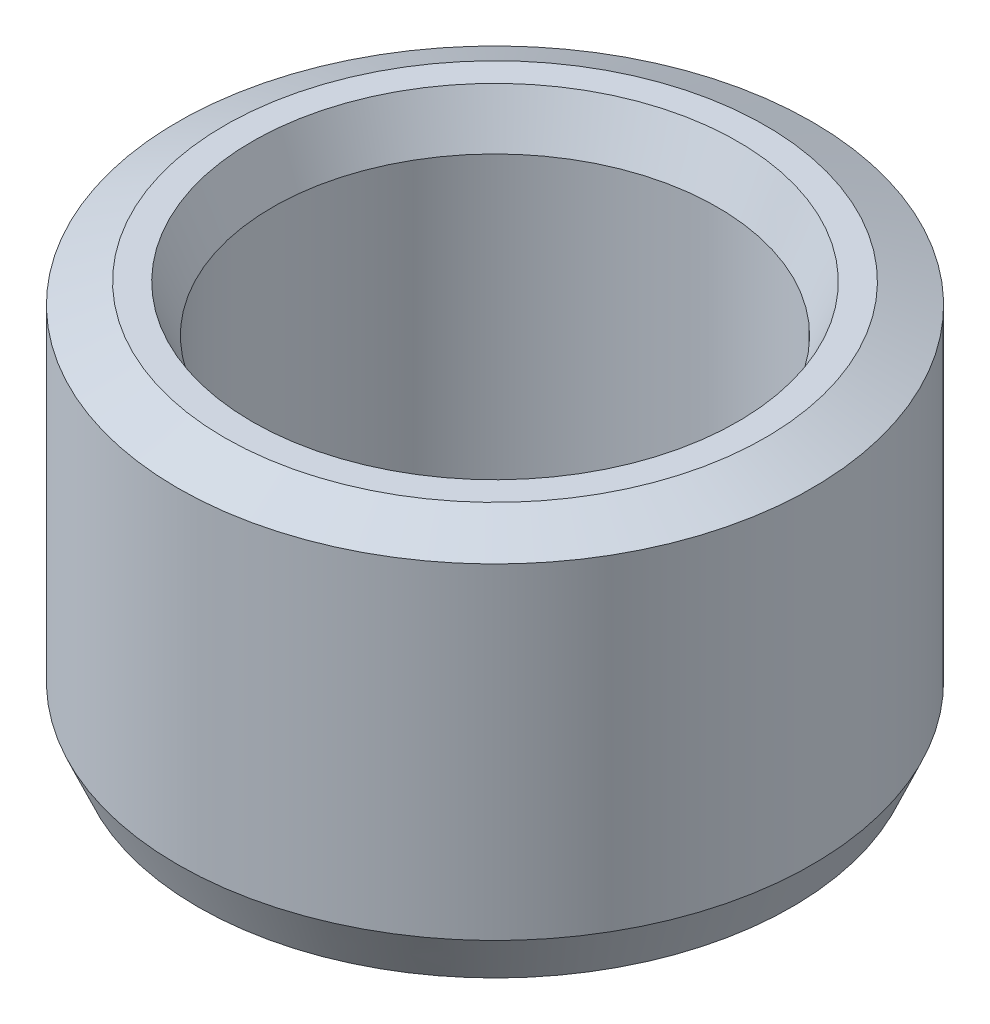
SolidWorks part; units mm, degrees
ref_plane "Front Plane" through (0, 0, 0) normal (0, 0, 1) x (1, 0, 0)
ref_plane "Top Plane" through (0, 0, 0) normal (0, 1, 0) x (1, 0, 0)
ref_plane "Right Plane" through (0, 0, 0) normal (1, 0, 0) x (0, 0, -1)
sketch "Sketch1" plane through (0, 0, 0) normal (0, 1, 0) x (1, 0, 0)
  circle A0 centre (0, 0) radius 37.5
  dimension "SLEEVE_OD" = 75
extrude "Boss-Extrude1" add sketch "Sketch1" along normal blind 46.4748
sketch "Sketch2" plane through (0, 0, 0) normal (0, 1, 0) x (1, 0, 0)
  circle A0 centre (0, 0) radius 26.3005
  dimension "BORE_D" = 52.601
extrude "Cut-Extrude1" cut sketch "Sketch2" along normal through all
chamfer "Chamfer1" distance 2.3966 angle 66.576 4 edges at (0, 46.4748, 26.3005) (0, 0, 26.3005) (0, 0, 37.5) (0, 46.4748, 37.5) first distance on face at (0, 46.4748, 26.3005) first distance on face at (0, 0, 26.3005) first distance on face at (0, 46.4748, 37.5)
